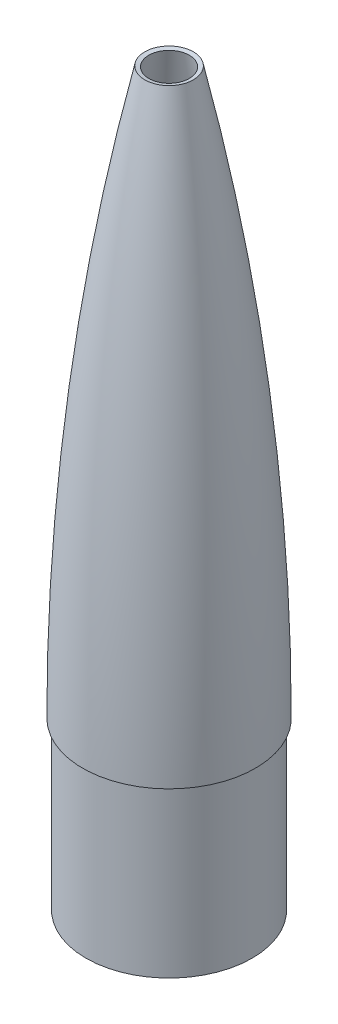
SolidWorks part; units mm, degrees
note: '?' marks a value the reader was unsure of.
material "E-Glass Fiber"
ref_plane "Front Plane" through (0, 0, 0) normal (0, 0, 1) x (1, 0, 0)
ref_plane "Top Plane" through (0, 0, 0) normal (0, 1, 0) x (1, 0, 0)
ref_plane "Right Plane" through (0, 0, 0) normal (1, 0, 0) x (0, 0, -1)
sketch "Sketch1" plane through (0, 0, 0) normal (0, 0, 1) x (1, 0, 0)
  line L0 (0, 0) -> (0, 508) construction
  line L1 (0, 431.8) -> (18.5515, 431.8) construction
  line L2 (66.04, 0) -> (63.5, 0)
  line L3 (63.5, 0) -> (63.5, -127)
  arc A0 (66.04, 0) -> (18.5515, 431.8) centre (-1920.8262, 0) ccw
  arc A1 (0, 508) -> (18.5515, 431.8) centre (-1920.8262, 0) cw construction
  dimension "D1" = 66.04
  dimension "D2" = 508
  dimension "D3" = 76.2
  dimension "D4" = 127
  dimension "D5" = 2.54
revolve "Revolve-Thin3" add sketch "Sketch1" angle 360 about L0
ref_axis "Axis1" through (0, 0, 0) along (0, -1, 0)?
